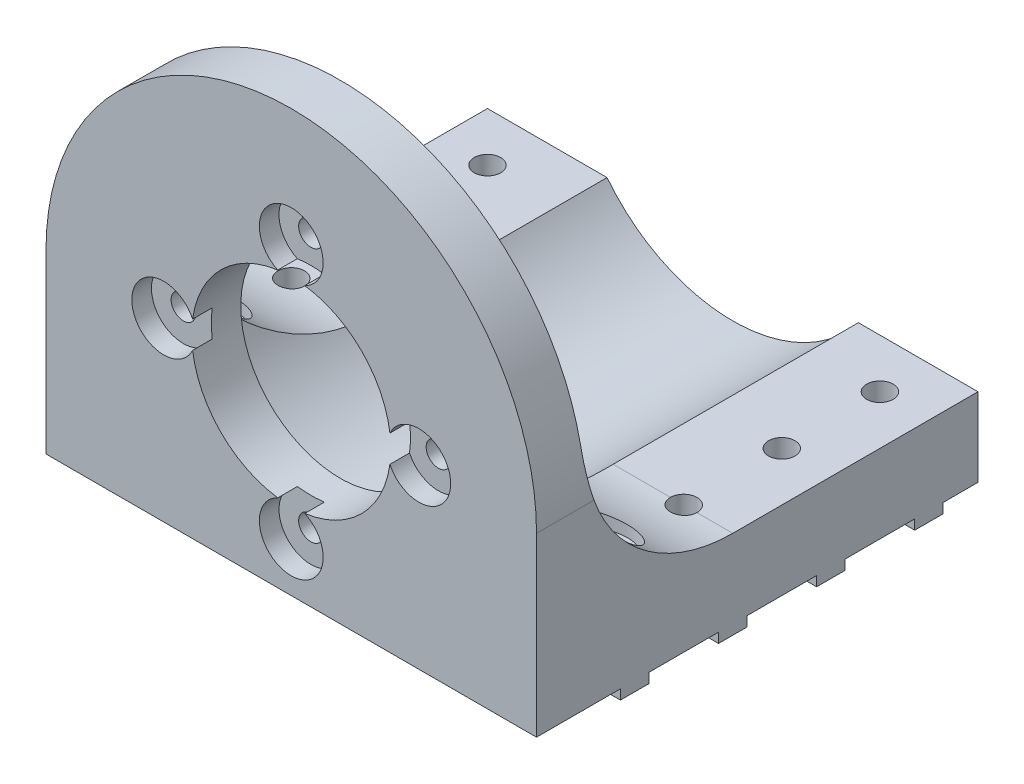
SolidWorks part; units mm, degrees
ref_plane "Front Plane" through (0, 0, 0) normal (0, 0, 1) x (1, 0, 0)
ref_plane "Top Plane" through (0, 0, 0) normal (0, 1, 0) x (1, 0, 0)
ref_plane "Right Plane" through (0, 0, 0) normal (1, 0, 0) x (0, 0, -1)
ref_axis "Axis1" through (0, 0, -24.2) along (0, 0, 1)
ref_axis "Axis2" through (0, -26.2, 0) along (0, 1, 0)
sketch "Sketch1" plane through (0, 0, 0) normal (0, 0, 1) x (1, 0, 0)
  line L0 (0, -26.2) -> (0, 22.2) construction
  line L12 (-25, -18) -> (-25, 0)
  line L17 (-25, -18) -> (25, -18)
  line L23 (25, -18) -> (25, 0)
  arc A0 (-25, 0) -> (25, 0) centre (0, 0) cw
  circle A1 centre (0, 0) radius 10.15
  point P0 (0, -18)
  dimension "D1" = 25
  dimension "D9" = 20.3
  dimension "D2" = 18
  dimension "D3" = 50
extrude "Main" add sketch "Sketch1" along normal blind 45
sketch "Sketch3" plane through (0, 0, 0) normal (0, 0, 1) x (1, 0, 0)
  circle A0 centre (0, 0) radius 16.25
  dimension "D1" = 32.5
extrude "MotoReductorMainHole" cut sketch "Sketch3" along normal blind 40
sketch "Sketch2" plane through (0, 0, 45) normal (0, 0, 1) x (1, 0, 0)
  circle A0 centre (0, 13) radius 1.25
  dimension "D2" = 2.5
  dimension "D1" = 13
extrude "FixHoleMotors" cut sketch "Sketch2" against normal blind 10
pattern_circular "HoleCircularPattern" count 4 every 90 about axis through (0, 0, -24.2) along (0, 0, 1) of "FixHoleMotors"
sketch "Sketch5" plane through (0, 0, 45) normal (0, 0, 1) x (1, 0, 0)
  circle A0 centre (0, 13) radius 3.25
  circle A1 centre (13, 0) radius 3.25
  circle A2 centre (0, -13) radius 3.25
  circle A3 centre (-13, 0) radius 3.25
  dimension "D1" = 6.5
extrude "HeadScrewHole" cut sketch "Sketch5" against normal blind 2
sketch "Sketch4" plane through (0, 0, 0) normal (0, 0, -1) x (-1, 0, 0)
  line L0 (-25, -18) -> (-25, 0) construction
  line L1 (-25, -10) -> (25, -10)
  line L2 (-25, -10) -> (-25, 25)
  line L3 (-25, 25) -> (25, 25)
  line L4 (25, -10) -> (25, 25)
  line L5 (25, 0) -> (25, -18) construction
  line L6 (25, -18) -> (-25, -18) construction
  arc A0 (25, 0) -> (-25, 0) centre (0, 0) ccw construction
  point P5 (-20, -10.7047)
  point P11 (20, -10.3221)
  dimension "D1" = 8
extrude "HorizontalCut" cut sketch "Sketch4" against normal up to surface (40 mm away) up to face at (1.25, -13, 40)
fillet "Fillet3" radius 15 2 edges at (18.9043, -10, 40) (-18.9043, -10, 40)
sketch "Sketch7" plane through (0, -18, 0) normal (0, -1, 0) x (-1, 0, 0)
  line L0 (25, -45) -> (25, 0) construction
  line L1 (25, -36.45) -> (-25, -36.45)
  line L2 (25, -36.45) -> (25, -33.55)
  line L3 (25, -33.55) -> (-25, -33.55)
  line L4 (-25, -36.45) -> (-25, -33.55)
  line L5 (-25, -45) -> (-25, 0) construction
  line L6 (25, -45) -> (-25, -45) construction
  point P8 (25, -35)
  dimension "D1" = 10
  dimension "D2" = 2.9
extrude "MakerBeamRail" add sketch "Sketch7" along normal blind 1
pattern_linear "LPattern1" count 4 spacing 10 along (0, 0, -1) of "MakerBeamRail"
ref_plane "Plane1" through (0, -10, 0) normal (0, 1, 0) x (1, 0, 0)
sketch "Sketch6" plane through (0, -19, 0) normal (0, -1, 0) x (-1, 0, 0)
  line L0 (25, -36.45) -> (25, -33.55) construction
  line L3 (0, 24.2) -> (0, -24.2) construction
  circle A0 centre (20, -35) radius 1.35
  circle A1 centre (20, -15) radius 1.35
  circle A2 centre (20, -25) radius 1.35
  circle A3 centre (20, -5) radius 1.35
  point P6 (20, -35)
  point P7 (25, -35)
  dimension "D1" = 2.7
  dimension "D2" = 20
  dimension "D4" = 10
  dimension "D5" = 10
  dimension "D7" = 20
extrude "FixToPlateHole" cut sketch "Sketch6" against normal through all
sketch "Sketch9" plane through (0, -10, 0) normal (0, 1, 0) x (1, 0, 0)
  circle A0 centre (-20, -35) radius 4.25
  dimension "D1" = 8.5
extrude "Cut-Extrude2" cut sketch "Sketch9" along normal through all
mirror "Mirror1" about plane through (0, 0, 0) normal (1, 0, 0) of "Cut-Extrude2", "FixToPlateHole"
